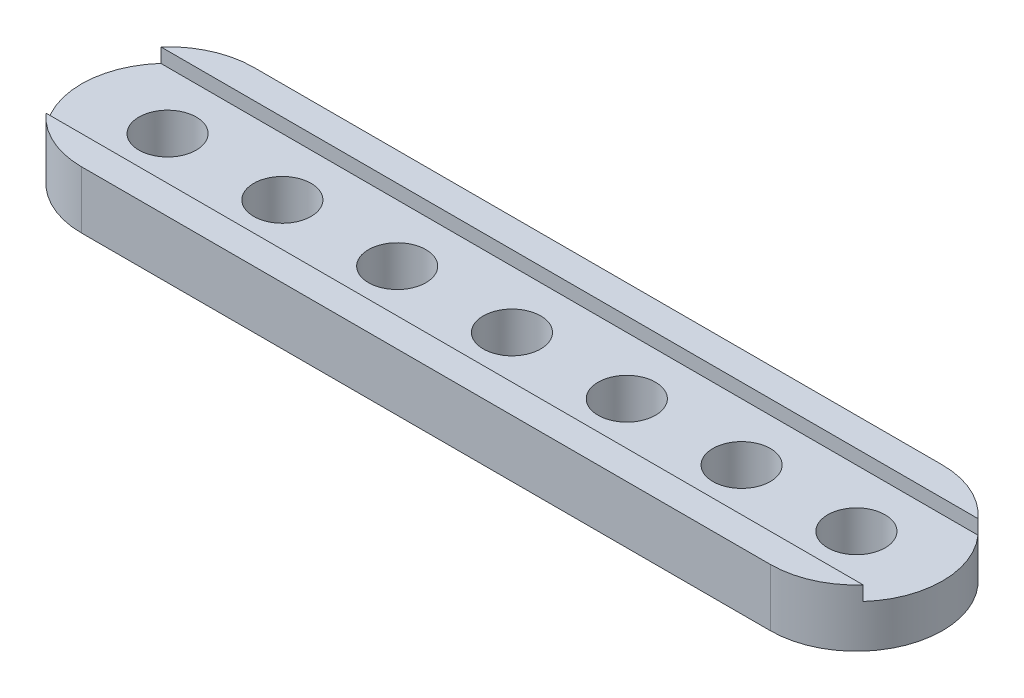
SolidWorks part; units mm, degrees
material "6061 Alloy"
ref_plane "前视基准面" through (0, 0, 0) normal (0, 0, 1) x (1, 0, 0)
ref_plane "上视基准面" through (0, 0, 0) normal (0, 1, 0) x (1, 0, 0)
ref_plane "右视基准面" through (0, 0, 0) normal (1, 0, 0) x (0, 0, -1)
other "Configuration Table"
sketch "Sketch1" plane through (0, 0, 0) normal (0, 1, 0) x (1, 0, 0)
  line L0 (24, 0) -> (-24, 0) construction
  line L1 (24, -6) -> (-24, -6)
  line L2 (24, 6) -> (-24, 6)
  line L3 (0, 6) -> (0, -6) construction
  arc A0 (24, -6) -> (24, 6) centre (24, 0) ccw
  arc A1 (-24, 6) -> (-24, -6) centre (-24, 0) ccw
  circle A2 centre (-24, 0) radius 2
  circle A3 centre (-16, 0) radius 2
  circle A4 centre (-8, 0) radius 2
  circle A5 centre (0, 0) radius 2
  circle A6 centre (8, 0) radius 2
  circle A7 centre (16, 0) radius 2
  circle A8 centre (24, 0) radius 2
  point P2 (0, 0)
  dimension "D1" = 8
  dimension "D2" = 8
  dimension "D3" = 8
extrude "Boss-Extrude1" add sketch "Sketch1" along normal blind 4
sketch "Sketch2" plane through (0, 0, 0) normal (1, 0, 0) x (0, 0, -1)
  line L5 (6, 4) -> (-6, 4) construction
  line L6 (4, 3) -> (-4, 3)
  line L7 (4, 3) -> (4, 4)
  line L8 (4, 4) -> (-4, 4)
  line L9 (-4, 3) -> (-4, 4)
  line L10 (4, 3) -> (-4, 4) construction
  line L11 (4, 4) -> (-4, 3) construction
  point P0 (0, 3.5)
  dimension "D1" = 1
  dimension "D2" = 8
extrude "Cut-Extrude1" cut sketch "Sketch2" against normal blind 32
extrude "Cut-Extrude2" cut sketch "Sketch2<2>" along normal blind 35
sketch "Sketch2<2>" plane through (0, 0, 0) normal (1, 0, 0) x (0, 0, -1) same geometry as "Sketch2"
